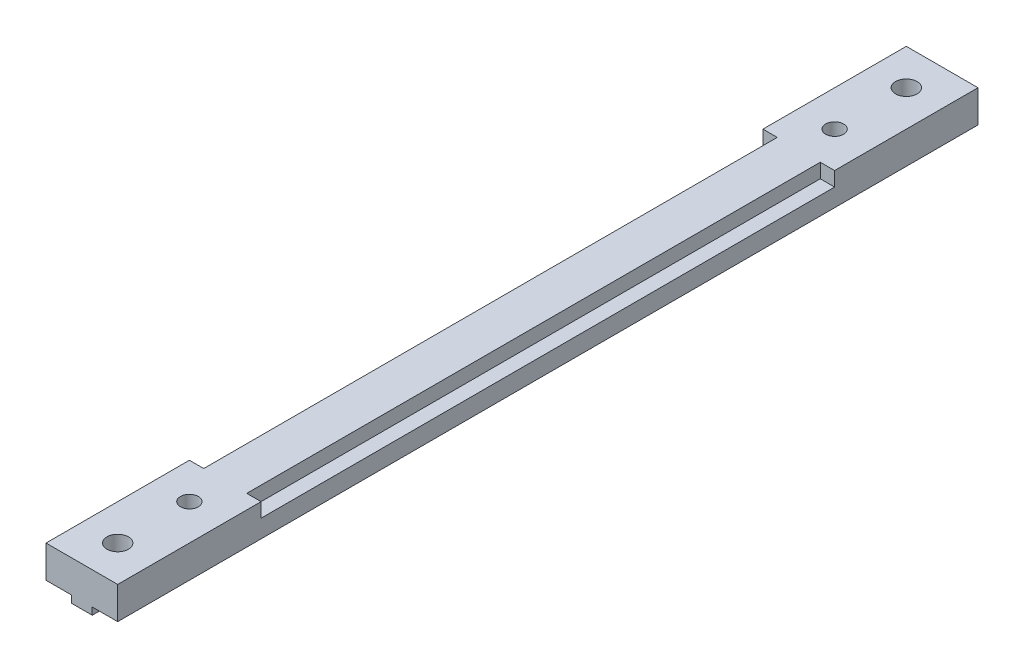
SolidWorks part; units mm, degrees
ref_plane "Front Plane" through (0, 0, 0) normal (0, 0, 1) x (1, 0, 0)
ref_plane "Top Plane" through (0, 0, 0) normal (0, 1, 0) x (1, 0, 0)
ref_plane "Right Plane" through (0, 0, 0) normal (1, 0, 0) x (0, 0, -1)
sketch "Sketch1" plane through (0, 0, 0) normal (0, 0, 1) x (1, 0, 0)
  line L0 (-5, 0) -> (5, 0)
  line L1 (5, 0) -> (5, -4.5)
  line L2 (5, -4.5) -> (1.45, -4.5)
  line L3 (1.45, -4.5) -> (1.45, -5.5)
  line L4 (1.45, -5.5) -> (-1.45, -5.5)
  line L5 (-1.45, -5.5) -> (-1.45, -4.5)
  line L6 (-1.45, -4.5) -> (-5, -4.5)
  line L7 (-5, -4.5) -> (-5, 0)
  point P9 (0, 0)
  dimension "D1" = 10
  dimension "D2" = 4.5
  dimension "D3" = 1
  dimension "D4" = 2.9
extrude "Main" add sketch "Sketch1" along normal blind 120
sketch "Sketch2" plane through (0, 0, 0) normal (0, 1, 0) x (1, 0, 0)
  line L0 (5, -120) -> (-5, -120) construction
  line L1 (5, 0) -> (-5, 0) construction
  circle A0 centre (0, -105) radius 1.25
  circle A1 centre (0, -15) radius 1.25
  circle A2 centre (0, -5) radius 1.5
  circle A3 centre (0, -115) radius 1.5
  dimension "D1" = 2.5
  dimension "D4" = 3
  dimension "D2" = 15
  dimension "D3" = 90
  dimension "D5" = 5
  dimension "D6" = 5
extrude "MainHoles" cut sketch "Sketch2" against normal through all
sketch "Sketch3" plane through (0, 0, 0) normal (0, 1, 0) x (1, 0, 0)
  line L0 (-5, -120) -> (-5, 0) construction
  line L1 (-5, -20) -> (-3, -20)
  line L2 (-5, -20) -> (-5, -100)
  line L3 (-5, -100) -> (-3, -100)
  line L4 (-3, -20) -> (-3, -100)
  line L5 (5, -120) -> (5, 0) construction
  line L6 (3, -20) -> (5, -20)
  line L7 (3, -20) -> (3, -100)
  line L8 (3, -100) -> (5, -100)
  line L9 (5, -20) -> (5, -100)
  line L10 (5, -120) -> (-5, -120) construction
  dimension "D1" = 6
  dimension "D2" = 80
  dimension "D3" = 20
extrude "PinHoles" cut sketch "Sketch3" against normal blind 2
